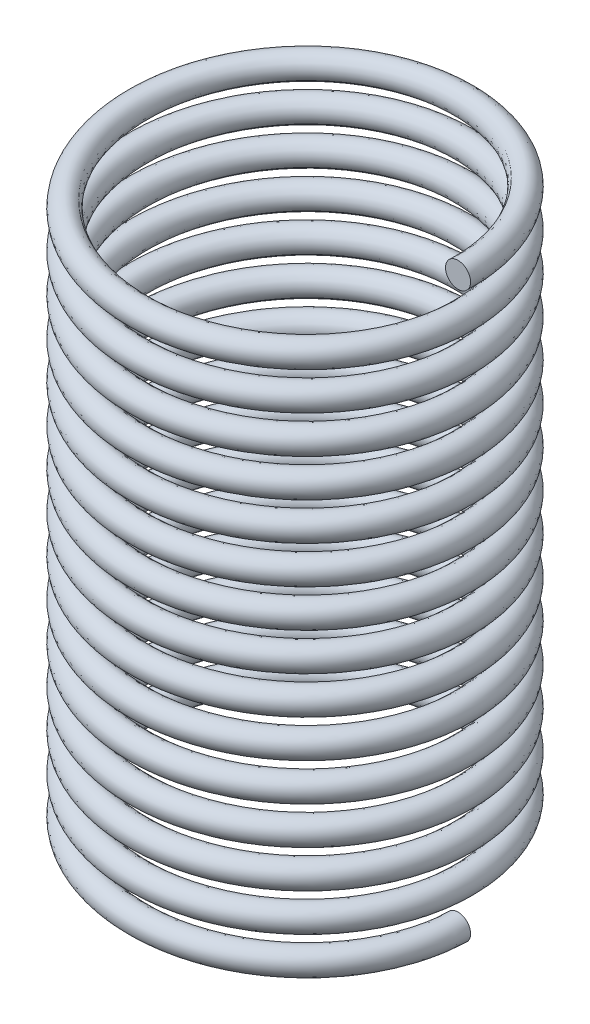
SolidWorks part; units mm, degrees
note: '?' marks a value the reader was unsure of.
ref_plane "前视基准面" through (0, 0, 0) normal (0, 0, 1) x (1, 0, 0)
ref_plane "上视基准面" through (0, 0, 0) normal (0, 1, 0) x (1, 0, 0)
ref_plane "右视基准面" through (0, 0, 0) normal (1, 0, 0) x (0, 0, -1)
sketch "草图1" plane through (0, 0, 0) normal (0, 1, 0) x (1, 0, 0)
  circle A0 centre (0, 0) radius 13
  dimension "D1" = 26
curve "螺旋线/涡状线1" pitch 3 height 45 turns 15
sketch "草图3" plane through (0, 0, 0) normal (0, 1, 0) x (1, 0, 0)
  circle A0 centre (0, 0) radius 20
ref_axis "基准轴1" through (13, 45, 0) along (0, 0, 1)?
sketch "草图4" plane through (0, 0, 0) normal (0, 0, 1) x (1, 0, 0)
  circle A0 centre (13, 45) radius 1
  point P3 (13, 45)
  dimension "D1" = 2
sweep "扫描1" add profiles "草图4" path "螺旋线/涡状线1"
